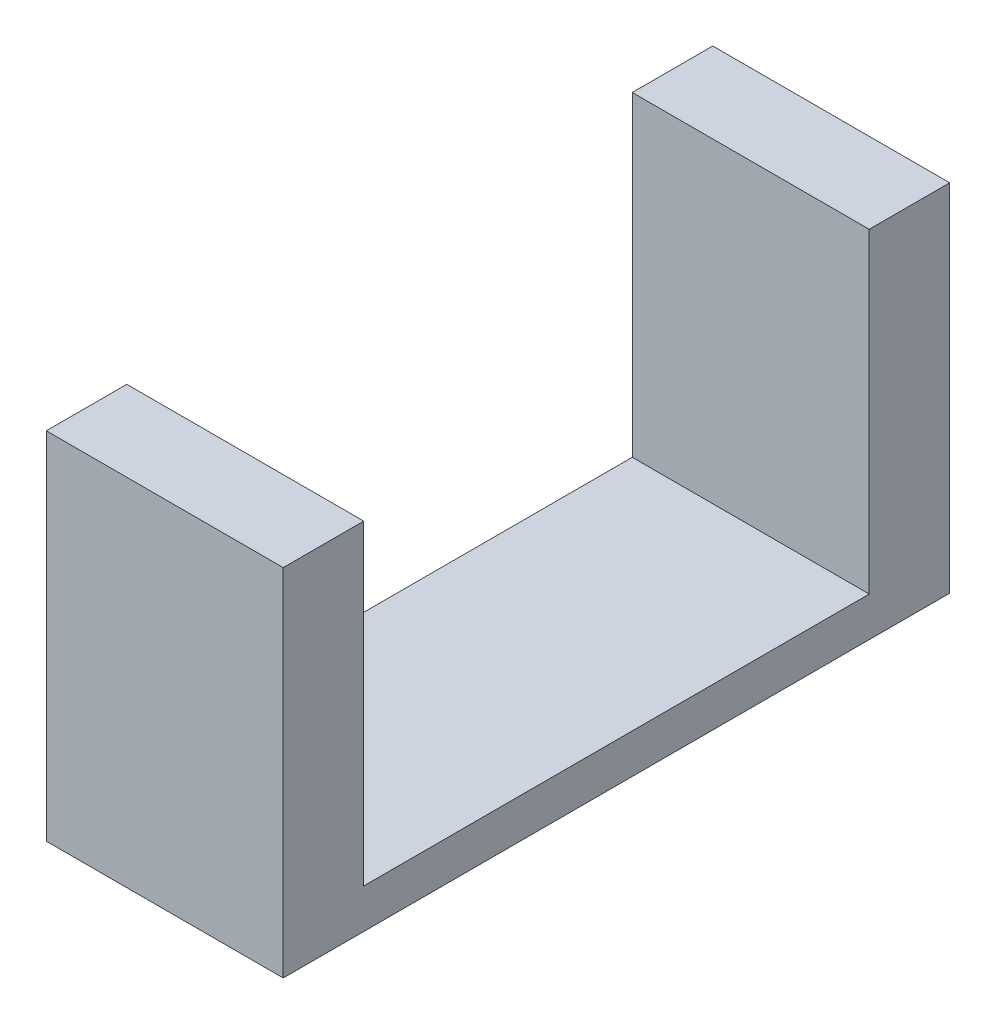
SolidWorks part; units mm, degrees
material "ABS"
ref_plane "Front Plane" through (0, 0, 0) normal (0, 0, 1) x (1, 0, 0)
ref_plane "Top Plane" through (0, 0, 0) normal (0, 1, 0) x (1, 0, 0)
ref_plane "Right Plane" through (0, 0, 0) normal (1, 0, 0) x (0, 0, -1)
sketch "Sketch1" plane through (0, 0, 0) normal (0, 1, 0) x (1, 0, 0)
  line L0 (-9.525, 20.32) -> (9.525, 20.32)
  line L1 (-9.525, -26.7921) -> (9.525, -26.7921)
  line L2 (-9.525, -26.7921) -> (-9.525, 26.7921)
  line L3 (-9.525, 26.7921) -> (9.525, 26.7921)
  line L4 (9.525, -26.7921) -> (9.525, 26.7921)
  line L5 (-9.525, -26.7921) -> (9.525, 26.7921) construction
  line L6 (-9.525, 26.7921) -> (9.525, -26.7921) construction
  line L7 (-9.525, -20.32) -> (9.525, -20.32)
  line L8 (0, -26.7921) -> (0, -20.32) construction
  line L9 (0, 26.7921) -> (0, 20.32) construction
  point P0 (0, 0)
  point P14 (9.525, -26.7921)
  dimension "D1" = 40.64
  dimension "D2" = 19.05
extrude "Boss-Extrude1" add sketch "Sketch1" along normal blind 3.175 contours L2 L7 L4 L0 | L0 L4 L3 L2 | L7 L2 L1 L4 region at (0, 0, -23.556) region at (0, 0, 0) region at (0, 0, 23.556)
extrude "Boss-Extrude2" add sketch "Sketch1<3>" along normal blind 28.575 contours L0 L4 L3 L2 | L7 L2 L1 L4 region at (0, 0, -23.556) region at (0, 0, 23.556)
sketch "Sketch1<3>" plane through (0, 0, 0) normal (0, 1, 0) x (1, 0, 0) same geometry as "Sketch1"
